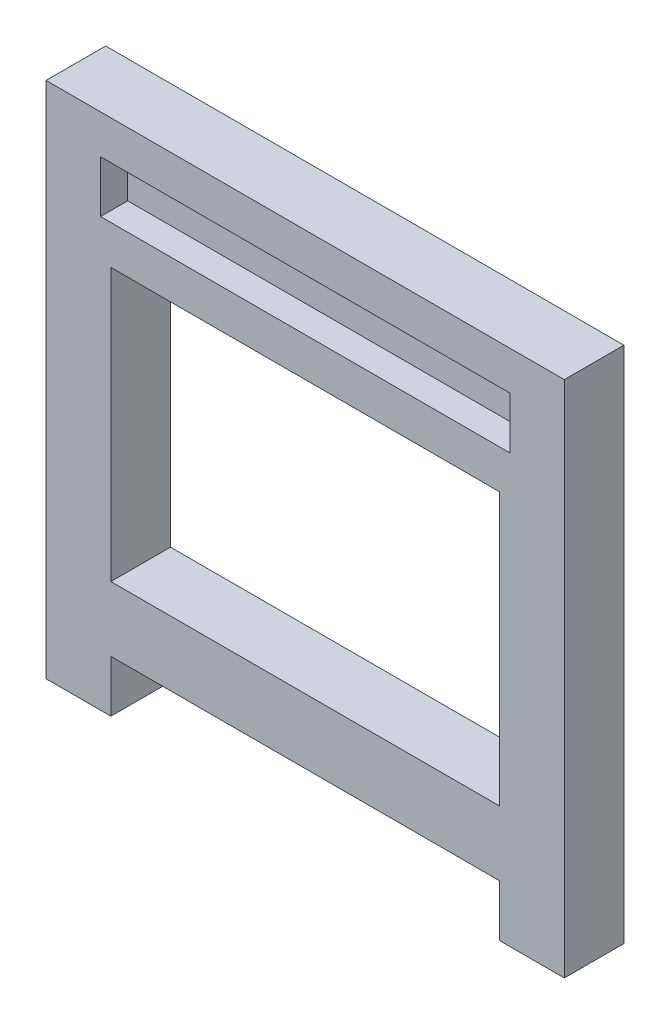
SolidWorks part; units mm, degrees
ref_plane "Front Plane" through (0, 0, 0) normal (0, 0, 1) x (1, 0, 0)
ref_plane "Top Plane" through (0, 0, 0) normal (0, 1, 0) x (1, 0, 0)
ref_plane "Right Plane" through (0, 0, 0) normal (1, 0, 0) x (0, 0, -1)
sketch "Sketch1" plane through (0, 0, 0) normal (0, 0, 1) x (1, 0, 0)
  line L0 (0, 0) -> (0, -2)
  line L1 (2.5, 0) -> (17.5, 0)
  line L2 (0, 0) -> (0, 18)
  line L3 (0, 18) -> (20, 18)
  line L4 (20, 0) -> (20, 18)
  line L5 (0, -2) -> (2.5, -2)
  line L6 (2.5, -2) -> (2.5, 0)
  line L7 (20, 0) -> (20, -2)
  line L8 (20, -2) -> (17.5, -2)
  line L9 (17.5, -2) -> (17.5, 0)
  line L12 (2.5, 2.5) -> (17.5, 2.5)
  line L13 (2.5, 2.5) -> (2.5, 13)
  line L14 (2.5, 13) -> (17.5, 13)
  line L15 (17.5, 2.5) -> (17.5, 13)
  line L16 (2.1, 14.5) -> (17.9, 14.5)
  line L17 (2.1, 14.5) -> (2.1, 16.5)
  line L18 (2.1, 16.5) -> (17.9, 16.5)
  line L19 (17.9, 14.5) -> (17.9, 16.5)
  dimension "D1" = 18
  dimension "D2" = 20
  dimension "D4" = 2
  dimension "D5" = 2
  dimension "D6" = 2.5
  dimension "D7" = 2.5
  dimension "D8" = 10.5
  dimension "D9" = 2
  dimension "D10" = 1.5
  dimension "D11" = 15.8
extrude "Boss-Extrude1" add sketch "Sketch1" along normal blind 2.3
extrude "Boss-Extrude2" add sketch "Sketch1<2>" along normal blind 1.25 contours L16 L19 L18 L17
sketch "Sketch1<2>" plane through (0, 0, 0) normal (0, 0, 1) x (1, 0, 0) same geometry as "Sketch1"
